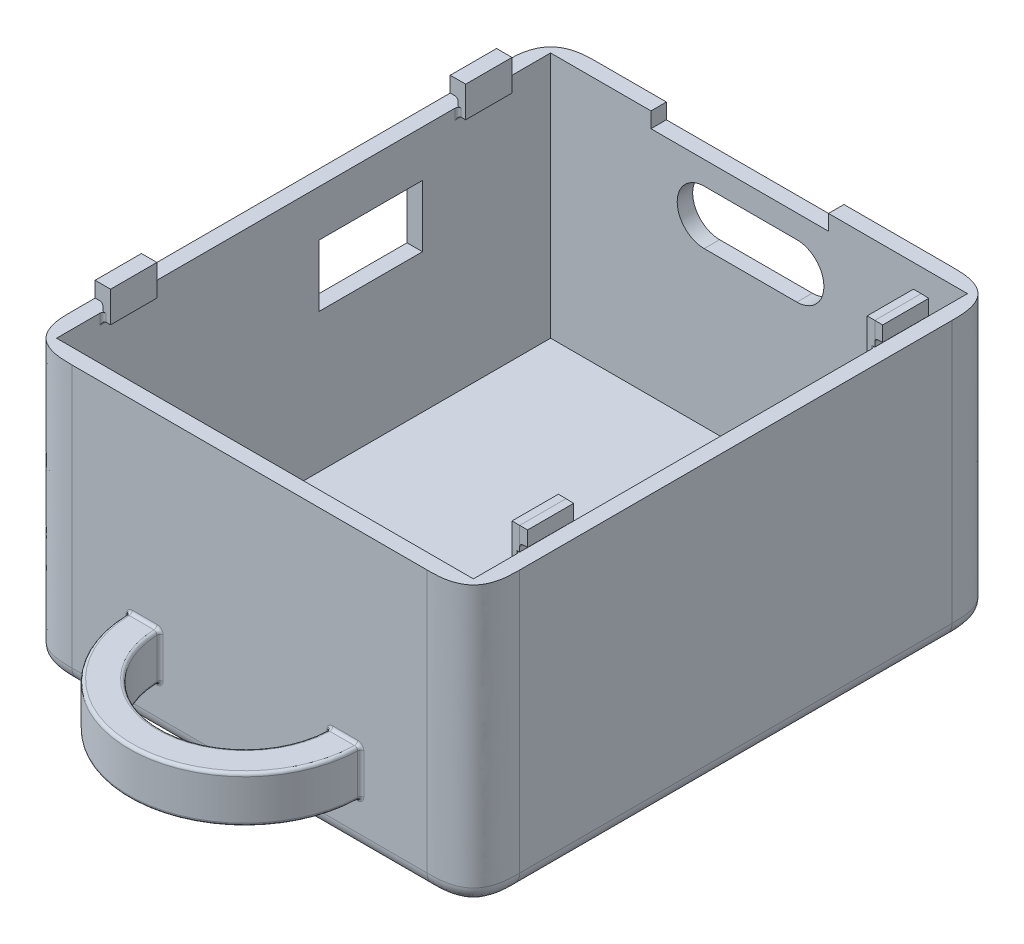
SolidWorks part; units mm, degrees
ref_plane "Front Plane" through (0, 0, 0) normal (0, 0, 1) x (1, 0, 0)
ref_plane "Top Plane" through (0, 0, 0) normal (0, 1, 0) x (1, 0, 0)
ref_plane "Right Plane" through (0, 0, 0) normal (1, 0, 0) x (0, 0, -1)
sketch "Sketch1" plane through (0, 0, 0) normal (0, 1, 0) x (1, 0, 0)
  line L1 (-148.5843, 96.7753) -> (-119.5843, 96.7753)
  line L2 (-148.5843, 96.7753) -> (-148.5843, 62.7753)
  line L3 (-148.5843, 62.7753) -> (-119.5843, 62.7753)
  line L4 (-119.5843, 96.7753) -> (-119.5843, 62.7753)
  dimension "D1" = 29
  dimension "D2" = 34
extrude "Bottom-Extrude" add sketch "Sketch1" along normal blind 18
fillet "Sid_Corner-Fillet" radius 3 4 edges at (-119.5843, 9, -62.7753) (-148.5843, 9, -62.7753) (-119.5843, 9, -96.7753) (-148.5843, 9, -96.7753) curvature continuous yes
fillet "Bottom-Fillet" radius 1 8 edges
sketch "Sketch2" plane through (0, 18, 0) normal (0, 1, 0) x (1, 0, 0)
  line L0 (-122.5843, 96.7753) -> (-145.5843, 96.7753) construction
  line L1 (-147.5843, 95.7753) -> (-120.5843, 95.7753)
  line L2 (-147.5843, 95.7753) -> (-147.5843, 63.7753)
  line L3 (-147.5843, 63.7753) -> (-120.5843, 63.7753)
  line L4 (-120.5843, 95.7753) -> (-120.5843, 63.7753)
  line L5 (-145.5843, 62.7753) -> (-122.5843, 62.7753) construction
  line L6 (-148.5843, 93.7753) -> (-148.5843, 65.7753) construction
  line L7 (-119.5843, 65.7753) -> (-119.5843, 93.7753) construction
  dimension "D1" = 1
  dimension "D2" = 1
  dimension "D3" = 1
  dimension "D4" = 1
extrude "Cut-Extrude1" cut sketch "Sketch2" against normal blind 16
ref_plane "Plane7" through (0, 0, -62.7753) normal (0, 0, 1) x (1, 0, 0)
ref_plane "Plane8" through (0, 1, 0) normal (0, 1, 0) x (1, 0, 0)
ref_plane "Plane9" through (0, 3, 0) normal (0, -1, 0) x (-1, 0, 0)
sketch "Sketch21" plane through (0, 3, 0) normal (0, -1, 0) x (-1, 0, 0)
  line L0 (-7.8811, 62.7753) -> (7.8811, 62.7753) construction
  line L1 (141.8802, 62.7753) -> (126.8802, 62.7753)
  arc A0 (126.8802, 62.7753) -> (141.8802, 62.7753) centre (134.3802, 62.7753) ccw
  arc A1 (128.8802, 62.7753) -> (139.8802, 62.7753) centre (134.3802, 62.7753) ccw
  dimension "D1" = 15
  dimension "D2" = 2
  dimension "D3" = 5.5
extrude "Boss-Extrude1" add sketch "Sketch21" against normal blind 3 contours A1 L1 A0 region at (-134.3802, 3, -55.443)
fillet "Fillet1" radius 0.2 12 edges at (-139.8802, 4.5, -62.7753) (-128.8802, 4.5, -62.7753) (-127.8802, 6, -62.7753) (-140.8802, 6, -62.7753) (-134.3802, 6, -57.2753) (-141.8802, 4.5, -62.7753) (-134.3802, 6, -55.2753) (-126.8802, 4.5, -62.7753) (-140.8802, 3, -62.7753) (-134.3802, 3, -55.2753) (-127.8802, 3, -62.7753) (-134.3802, 3, -57.2753)
sketch "Sketch22" plane through (0, 0, -96.7753) normal (0, 0, -1) x (-1, 0, 0)
  line L0 (131.6343, 13.75) -> (137.6343, 13.75) construction
  line L1 (131.6343, 15.5) -> (137.6343, 15.5)
  line L2 (131.6343, 12) -> (137.6343, 12)
  line L3 (122.5843, 18) -> (122.5843, 1) construction
  line L5 (145.5843, 1) -> (145.5843, 18) construction
  line L6 (122.5843, 18) -> (145.5843, 18) construction
  line L8 (129.5843, 18) -> (141.0843, 18)
  line L9 (129.5843, 18) -> (129.5843, 17)
  line L10 (129.5843, 17) -> (141.0843, 17)
  line L11 (141.0843, 18) -> (141.0843, 17)
  arc A0 (131.6343, 15.5) -> (131.6343, 12) centre (131.6343, 13.75) ccw
  arc A1 (137.6343, 12) -> (137.6343, 15.5) centre (137.6343, 13.75) ccw
  point P2 (134.6343, 13.75)
  dimension "D1" = 6
  dimension "D3" = 9.05
  dimension "D4" = 2.5
  dimension "D5" = 7.95
  dimension "D2" = 3.5
  dimension "D6" = 11.5
  dimension "D7" = 7
  dimension "D8" = 1
  dimension "D9" = 1.5
extrude "Cut-USB" cut sketch "Sketch22" against normal up to next
sketch "Sketch23" plane through (-148.5843, 0, 0) normal (-1, 0, 0) x (0, 0, 1)
  line L0 (-65.7753, 1) -> (-65.7753, 18) construction
  line L1 (-87.4753, 15) -> (-80.7753, 15)
  line L2 (-87.4753, 15) -> (-87.4753, 11)
  line L3 (-87.4753, 11) -> (-80.7753, 11)
  line L4 (-80.7753, 15) -> (-80.7753, 11)
  line L5 (-93.7753, 18) -> (-65.7753, 18) construction
  dimension "D1" = 4
  dimension "D2" = 6.7
  dimension "D3" = 15
  dimension "D4" = 3
extrude "Cut-BT" cut sketch "Sketch23" against normal up to surface (1 mm away) up to face at (-147.5843, 10, -79.7753)
sketch "Sketch24" plane through (-120.5843, 0, 0) normal (-1, 0, 0) x (0, 0, 1)
  line L0 (-63.7753, 18) -> (-95.7753, 18) construction
  line L1 (-69.7753, 19.5) -> (-66.7753, 19.5)
  line L2 (-69.7753, 19.5) -> (-69.7753, 17.5)
  line L3 (-69.7753, 17.5) -> (-66.7753, 17.5)
  line L4 (-66.7753, 19.5) -> (-66.7753, 17.5)
  line L5 (-63.7753, 2) -> (-63.7753, 18) construction
  dimension "D1" = 3
  dimension "D2" = 2
  dimension "D3" = 0.5
  dimension "D4" = 3
extrude "Boss-Clip" add sketch "Sketch24" along normal blind 0.5
sketch "Sketch26" plane through (-120.5843, 0, 0) normal (1, 0, 0) x (0, 0, -1)
  line L0 (66.7753, 18) -> (66.7753, 19.5) construction
  line L1 (66.7753, 19.5) -> (69.7753, 19.5)
  line L2 (66.7753, 19.5) -> (66.7753, 18.5)
  line L3 (66.7753, 18.5) -> (69.7753, 18.5)
  line L4 (69.7753, 19.5) -> (69.7753, 18.5)
  line L5 (69.7753, 19.5) -> (69.7753, 18) construction
  line L6 (66.7753, 19.5) -> (69.7753, 19.5) construction
  dimension "D1" = 3
  dimension "D2" = 1
  dimension "D3" = 0
extrude "Boss-ClipExt" add sketch "Sketch26" along normal blind 0.5 draft 1
fillet "Fillet2" radius 0.2 4 edges at (-120.5843, 17.75, -69.7753) (-120.5843, 17.75, -66.7753) (-120.5843, 17.5, -68.2753) (-120.5843, 18.5, -68.2753)
pattern_linear "LPattern2" count 2 spacing 23 along (0, 0, -1) of "Boss-Clip", "Boss-ClipExt", "Fillet2"
sketch "Sketch27" plane through (-147.5843, 0, 0) normal (1, 0, 0) x (0, 0, -1)
  line L0 (95.7753, 18) -> (63.7753, 18) construction
  line L1 (66.7753, 19.5) -> (69.7753, 19.5)
  line L2 (66.7753, 19.5) -> (66.7753, 17.5)
  line L3 (66.7753, 17.5) -> (69.7753, 17.5)
  line L4 (69.7753, 19.5) -> (69.7753, 17.5)
  line L5 (63.7753, 2) -> (63.7753, 18) construction
  dimension "D1" = 3
  dimension "D2" = 2
  dimension "D3" = 0.5
  dimension "D4" = 3
extrude "Boss-Clip1" add sketch "Sketch27" along normal blind 0.5
sketch "Sketch28" plane through (-147.5843, 0, 0) normal (-1, 0, 0) x (0, 0, 1)
  line L0 (-66.7753, 19.5) -> (-66.7753, 18) construction
  line L1 (-69.7753, 19.5) -> (-66.7753, 19.5)
  line L2 (-69.7753, 19.5) -> (-69.7753, 18.5)
  line L3 (-69.7753, 18.5) -> (-66.7753, 18.5)
  line L4 (-66.7753, 19.5) -> (-66.7753, 18.5)
  dimension "D1" = 1
  dimension "D2" = 0
extrude "Boss-ClipExt1" add sketch "Sketch28" along normal blind 0.5
fillet "Fillet4" radius 0.2 4 edges at (-147.5843, 18.5, -68.2753) (-147.5843, 17.75, -69.7753) (-147.5843, 17.5, -68.2753) (-147.5843, 17.75, -66.7753)
pattern_linear "LPattern4" count 2 spacing 23 along (0, 0, -1) of "Boss-Clip1", "Boss-ClipExt1", "Fillet4"
